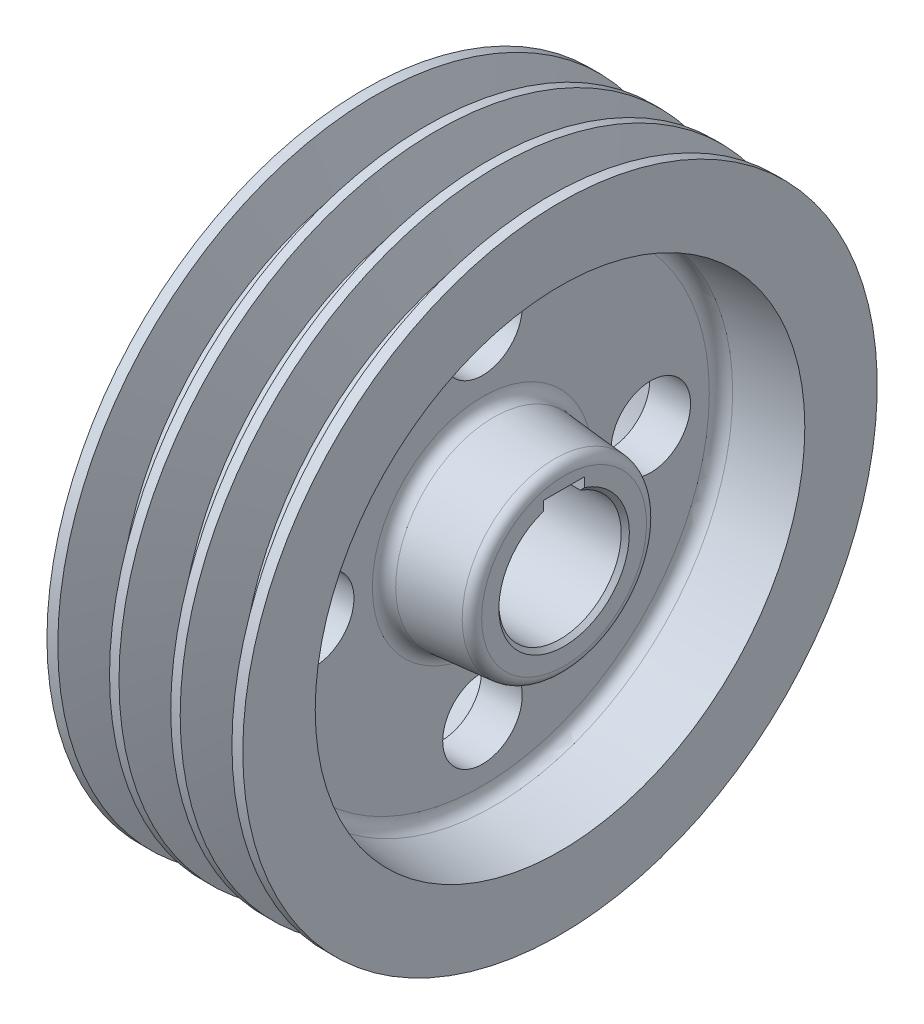
SolidWorks part; units mm, degrees
ref_plane "前视基准面" through (0, 0, 0) normal (0, 0, 1) x (1, 0, 0)
ref_plane "上视基准面" through (0, 0, 0) normal (0, 1, 0) x (1, 0, 0)
ref_plane "右视基准面" through (0, 0, 0) normal (1, 0, 0) x (0, 0, -1)
sketch "草图1" plane through (0, 0, 0) normal (0, 0, 1) x (1, 0, 0)
  line L0 (0, 0) -> (64.8368, 0) construction
  line L1 (-1, 15) -> (-1, 22.5)
  line L2 (0, 77.75) -> (48, 77.75)
  line L3 (48, 77.75) -> (48, 60)
  line L4 (-1, 22.5) -> (-30, 22.5) construction
  line L5 (19, 24.2498) -> (19, 58.3377)
  line L6 (49, 15) -> (-1, 15)
  line L7 (2.6592, 77.75) -> (6.1599, 66.3) construction
  line L8 (6.1599, 66.3) -> (11.8401, 66.3) construction
  line L9 (11.8401, 66.3) -> (15.3408, 77.75) construction
  line L10 (0, 75) -> (48, 75) construction
  line L11 (9, 66.3) -> (9, 15) construction
  line L12 (44, 60) -> (0, 60) construction
  line L13 (48, 60) -> (79, 60) construction
  line L14 (29, 58.3377) -> (29, 24.2498)
  line L15 (5, 22.5) -> (49, 22.5) construction
  line L16 (24, 15) -> (24, 77.75) construction
  line L17 (49, 22.5) -> (49, 15)
  line L18 (0, 60) -> (0, 77.75)
  line L19 (19, 51) -> (29, 51) construction
  line L20 (19, 31.5) -> (29, 31.5) construction
  line L21 (48, 60) -> (48, 51) construction
  line L22 (48, 51) -> (29, 51) construction
  line L23 (29, 31.5) -> (49, 31.5) construction
  line L24 (49, 31.5) -> (49, 22.5) construction
  line L25 (29, 58.3377) -> (48, 60)
  line L26 (19, 58.3377) -> (0, 60)
  line L27 (19, 24.2498) -> (-1, 22.5)
  line L28 (29, 24.2498) -> (49, 22.5)
  point P17 (3.5, 75)
  point P18 (14.5, 75)
  dimension "d2" = 120
  dimension "L" = 50
  dimension "B" = 48
  dimension "d" = 30
  dimension "d1" = 45
  dimension "D3" = 5
  dimension "D4" = 5
  dimension "dd" = 150
  dimension "f" = 9
  dimension "槽轮角" = 34
  dimension "bd" = 11
  dimension "hf" = 8.7
  dimension "ha" = 2.75
  dimension "da" = 155.5
  dimension "S" = 10
  dimension "S2" = 9
revolve "旋转1" add sketch "草图1" angle 360 about L0
sketch "草图2" plane through (0, 0, 0) normal (0, 0, 1) x (1, 0, 0)
  line L0 (11.8401, 66.3) -> (15.3408, 77.75) construction
  line L1 (6.1599, 66.3) -> (11.8401, 66.3) construction
  line L2 (2.6592, 77.75) -> (6.1599, 66.3) construction
  line L3 (11.8401, 66.3) -> (15.3408, 77.75)
  line L4 (6.1599, 66.3) -> (11.8401, 66.3)
  line L5 (2.6592, 77.75) -> (6.1599, 66.3)
  line L6 (2.6592, 77.75) -> (15.3408, 77.75)
  line L7 (0, 0) -> (123, 0) construction
revolve "切除-旋转1" cut sketch "草图2" angle 360 about L7
pattern_linear "轮槽数" count 3 spacing 15 along (1, 0, 0) of "切除-旋转1"
chamfer "倒角1" distance 1 angle 45 2 edges at (-1, 0, 15) (49, 0, 15)
sketch "草图4" plane through (-1, 0, 0) normal (-1, 0, 0) x (0, 0, 1)
  line L1 (-5, 14.1421) -> (5, 14.1421)
  line L2 (-5, 14.1421) -> (-5, 17.5)
  line L3 (-5, 17.5) -> (5, 17.5)
  line L4 (5, 14.1421) -> (5, 17.5)
  circle A0 centre (0, 0) radius 15 construction
  point P6 (2.5, 17.5)
  dimension "键槽高度" = 17.5
  dimension "键槽宽度" = 10
  dimension "t1" = 2.5
extrude "切除-拉伸1" cut sketch "草图4" against normal through all
fillet "圆角1" radius 3 4 edges at (29, 0, 58.3377) (19, 0, 24.2498) (19, 0, 58.3377) (29, 0, 24.2498)
fillet "圆角2" radius 2.5 2 edges at (49, 0, 22.5) (-1, 0, 22.5)
sketch "草图5" plane through (0, 0, 0) normal (1, 0, 0) x (0, 0, -1)
  line L0 (0, 66.3) -> (0, 15) construction
  circle A0 centre (0, 41.25) radius 9.75
extrude "切除-拉伸2" cut sketch "草图5" along normal through all
pattern_circular "圆孔个数" count 4 over 360 about axis through (0, 0, 0) along (-1, 0, 0) of "切除-拉伸2"
equation "\"B@草图1\" =  ( \"z@轮槽数\" - 1 )  * \"e@轮槽数\" +2 *  \"f@草图1\""
equation "\"键槽高度@草图4\" = \"d@草图1\" / 2 + \"t1@草图4\""
